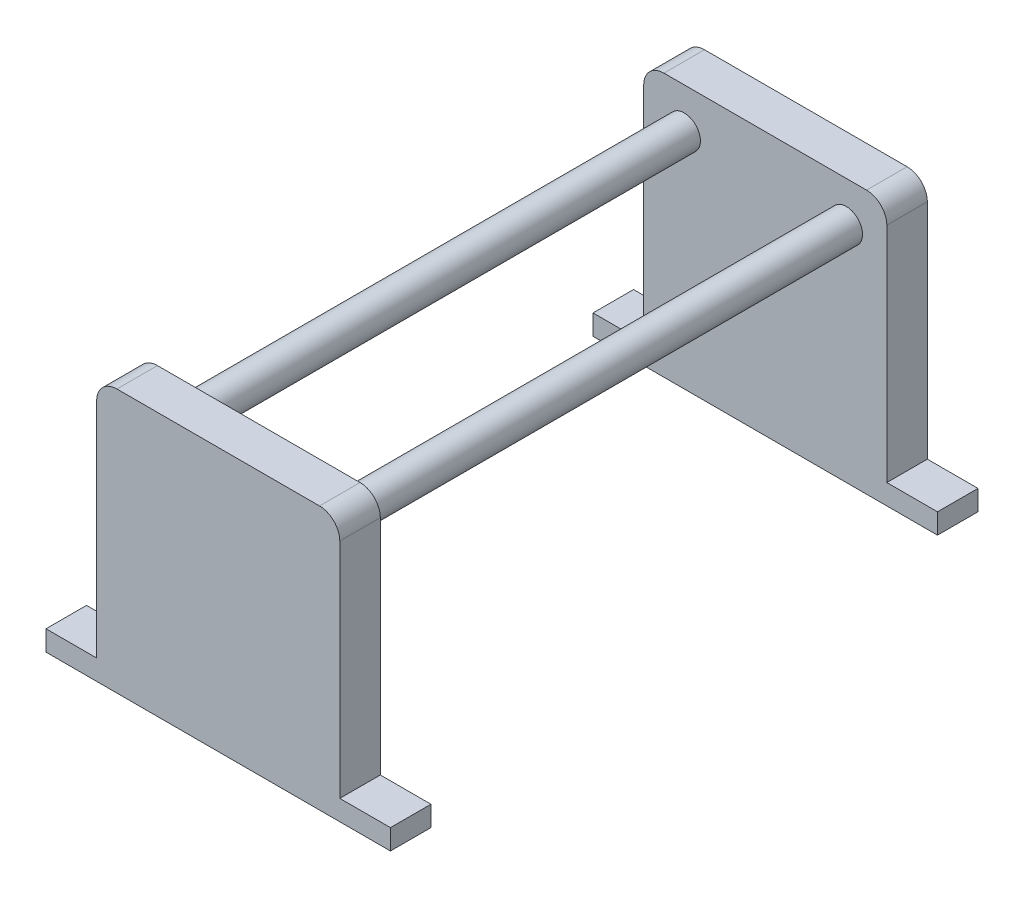
SolidWorks part; units mm, degrees
ref_plane "Alzado" through (0, 0, 0) normal (0, 0, 1) x (1, 0, 0)
ref_plane "Planta" through (0, 0, 0) normal (0, 1, 0) x (1, 0, 0)
ref_plane "Vista lateral" through (0, 0, 0) normal (1, 0, 0) x (0, 0, -1)
sketch "Croquis1" plane through (0, 0, 0) normal (0, 0, 1) x (1, 0, 0)
  line L1 (30, 30) -> (-30, 30)
  line L2 (30, 30) -> (30, -30)
  line L3 (30, -30) -> (-30, -30)
  line L4 (-30, 30) -> (-30, -30)
  line L5 (30, 30) -> (-30, -30) construction
  line L6 (30, -30) -> (-30, 30) construction
  line L7 (-42.5, -30) -> (42.5, -30)
  line L8 (-42.5, -30) -> (-42.5, -35)
  line L9 (-42.5, -35) -> (42.5, -35)
  line L10 (42.5, -30) -> (42.5, -35)
  line L11 (-42.5, -30) -> (42.5, -35) construction
  line L12 (-42.5, -35) -> (42.5, -30) construction
  point P0 (0, 0)
  point P10 (0, -32.5)
  dimension "D1" = 60
  dimension "D2" = 5
  dimension "D3" = 85
extrude "Saliente-Extruir1" add sketch "Croquis1" along normal blind 10 contours L1 L4 L3 L2 | L10 L7 L3 L8 L9 region at (0, 0, 0) region at (0, -32.5, 0)
fillet "Redondeo1" radius 5 2 edges at (30, 30, 5) (-30, 30, 5)
sketch "Croquis2" plane through (0, 0, 0) normal (0, 0, -1) x (-1, 0, 0)
  line L0 (0, 30) -> (0, -35) construction
  line L1 (-25, 30) -> (25, 30) construction
  line L2 (42.5, -35) -> (-42.5, -35) construction
  line L3 (-30, 25) -> (-30, -30) construction
  circle A0 centre (-20, 20) radius 4
  circle A1 centre (20, 20) radius 4
  dimension "D1" = 10
  dimension "D3" = 8
  dimension "D2" = 10
extrude "Saliente-Extruir2" add sketch "Croquis2" along normal blind 125
sketch "Croquis3" plane through (0, 0, -125) normal (0, 0, -1) x (-1, 0, 0)
  line L1 (-30, 30) -> (30, 30)
  line L2 (-30, 30) -> (-30, -30)
  line L3 (-30, -30) -> (30, -30)
  line L4 (30, 30) -> (30, -30)
  line L5 (-30, 30) -> (30, -30) construction
  line L6 (-30, -30) -> (30, 30) construction
  line L7 (42.5, -30) -> (-42.5, -30)
  line L8 (42.5, -30) -> (42.5, -35)
  line L9 (42.5, -35) -> (-42.5, -35)
  line L10 (-42.5, -30) -> (-42.5, -35)
  line L11 (42.5, -30) -> (-42.5, -35) construction
  line L12 (42.5, -35) -> (-42.5, -30) construction
  point P4 (0, 0)
  point P10 (0, -32.5)
  circle M2 centre (20, 20) radius 4
  dimension "D1" = 60
extrude "Saliente-Extruir4" add sketch "Croquis3" along normal blind 10 contours L4 L1 L2 L3 M2 | L7 L10 L9 L8 L3 | M2 region at (0.2832, -0.2832, -125) region at (0, -32.5, -125) region at (-20, 20, -125)
fillet "Redondeo2" radius 5 2 edges at (30, 30, -130) (-30, 30, -130)
